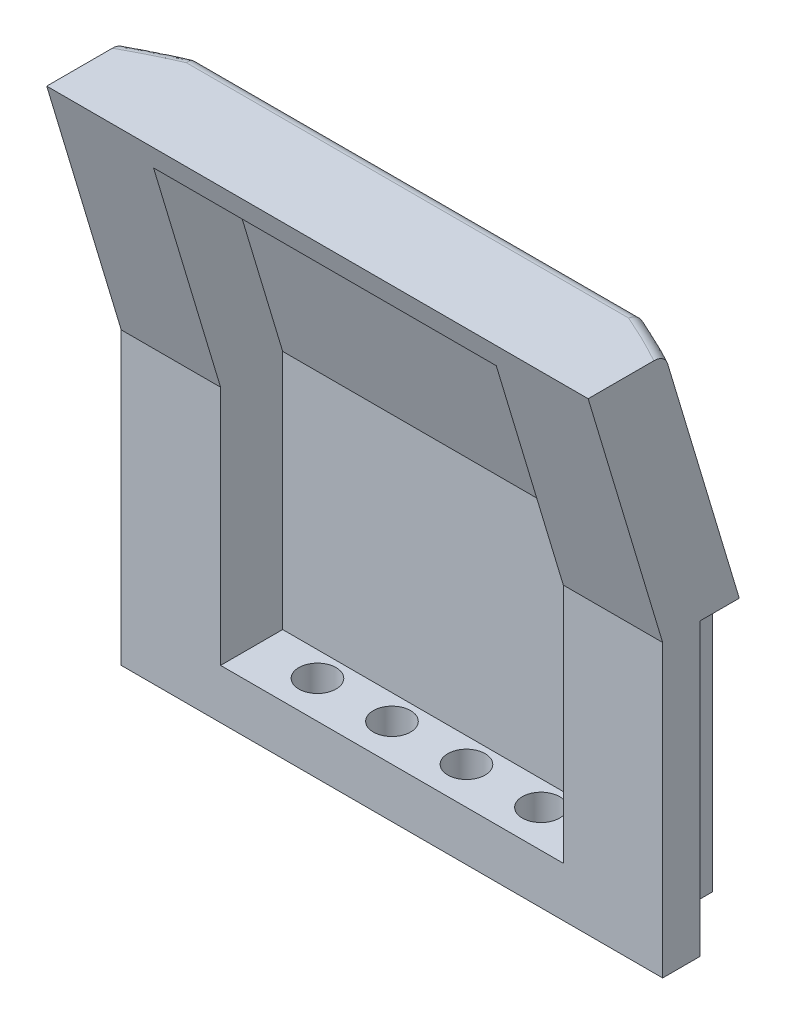
SolidWorks part; units mm, degrees
note: The reader was unsure of these and kept them because the rebuilt part matched: shared geometry of "Sketch1<4>", "Sketch1<7>", "Sketch2<5>", "Sketch2<6>", "Sketch2<7>", "Sketch2<8>".
ref_plane "Front Plane" through (0, 0, 0) normal (0, 0, 1) x (1, 0, 0)
ref_plane "Top Plane" through (0, 0, 0) normal (0, 1, 0) x (1, 0, 0)
ref_plane "Right Plane" through (0, 0, 0) normal (1, 0, 0) x (0, 0, -1)
sketch "Sketch1" plane through (0, 0, 0) normal (0, 1, 0) x (1, 0, 0)
  line L0 (0, 0) -> (3, 0) construction
  line L1 (3, 0) -> (6, 0) construction
  line L2 (6, 0) -> (9, 0) construction
  line L3 (13.4, 2.5) -> (-4.4, 2.5)
  line L4 (-6.4, -1.5) -> (15.4, -1.5)
  line L7 (-6.4, 0) -> (-6.4, -1.5)
  line L10 (13.4, 2.5) -> (13.4, 0)
  line L11 (13.4, 0) -> (15.4, 0)
  line L15 (-4.4, 1) -> (13.4, 1)
  line L16 (-2.4, -1.5) -> (-2.4, 1)
  line L17 (11.4, 1) -> (11.4, -1.5)
  line L18 (15.4, 0) -> (15.4, -1.5)
  line L19 (-4.4, 2.5) -> (-4.4, 0)
  line L20 (-4.4, 0) -> (-6.4, 0)
  circle A0 centre (3, 0) radius 0.75
  circle A1 centre (6, 0) radius 0.75
  circle A2 centre (9, 0) radius 0.75
  circle A3 centre (0, 0) radius 0.75
  circle A4 centre (0, 0) radius 1
  circle A5 centre (3, 0) radius 1
  circle A6 centre (6, 0) radius 1
  circle A7 centre (9, 0) radius 1
  point P29 (4.5, -1.5)
  point P30 (4.5, 0)
  dimension "D1" = 2
  dimension "D2" = 1.5
  dimension "D3" = 3
  dimension "D4" = 17.8
  dimension "D5" = 1.5
  dimension "D6" = 2
  dimension "D7" = 2
  dimension "D8" = 2
  dimension "D9" = 2.5
extrude "Boss-Extrude1" add sketch "Sketch1" along normal blind 1.7
extrude "Boss-Extrude2" add sketch "Sketch1<4>" against normal blind 0.3
sketch "Sketch1<4>" plane through (0, 0, 0) normal (0, 1, 0) x (1, 0, 0) same geometry as "Sketch1"
extrude "Boss-Extrude3" add sketch "Sketch1<7>" along normal blind 11.4
sketch "Sketch1<7>" plane through (0, 0, 0) normal (0, 1, 0) x (1, 0, 0) same geometry as "Sketch1"
sketch "Sketch2" plane through (-4.4, 0, 0) normal (-1, 0, 0) x (0, 0, 1)
  line L0 (-2.5, 11.4) -> (0.5, 21.4)
  line L1 (0.5, 21.4) -> (4.5, 21.4)
  line L2 (4.5, 21.4) -> (1.5, 11.4)
  line L3 (-2.5, 11.4) -> (1.5, 11.4)
  line L4 (-1, 11.4) -> (2, 21.4)
  line L5 (1.7, 20.4) -> (4.2, 20.4)
  line M6 (-2.5, 11.4) -> (-2.5, -0.3)
  line M7 (-2.5, -0.3) -> (0, -0.3)
  line M8 (0, -0.3) -> (0, 11.4)
  line M9 (0, 11.4) -> (-2.5, 11.4)
  dimension "D1" = 3
  dimension "D2" = 10
  dimension "D3" = 1.5
  dimension "D4" = 1
extrude "Boss-Extrude4" add sketch "Sketch2" against normal up to surface (19.8 mm away) contours L3 L4 L1 L0 | L4 L3 L2 L1 M9
extrude "Cut-Extrude1" cut sketch "Sketch2<5>" against normal up to surface (15.8 mm away) contours L4 L3 L2 L1 M9
sketch "Sketch2<5>" plane through (-4.4, 0, 0) normal (-1, 0, 0) x (0, 0, 1) same geometry as "Sketch2"
extrude "Boss-Extrude5" add sketch "Sketch2<6>" along direction (-1, 0, 0) on the side against the normal up to surface (2 mm away) contours L4 L3 L2 L1 M9 | L3 L4 L1 L0 | L3 M9 M6 M7 M8
sketch "Sketch2<6>" plane through (-4.4, 0, 0) normal (-1, 0, 0) x (0, 0, 1) same geometry as "Sketch2"
extrude "Boss-Extrude6" add sketch "Sketch2<7>" along normal up to surface (2 mm away) contours L4 L3 L2 L1 M9 | L3 L4 L1 L0
sketch "Sketch2<7>" plane through (-4.4, 0, 0) normal (-1, 0, 0) x (0, 0, 1) same geometry as "Sketch2"
ref_plane "Plane1" through (0, 19.7706, 5.9312) normal (0, 0.9578, 0.2873) x (1, 0, 0)
sketch "Sketch5" plane through (0, 19.7706, 5.9312) normal (0, 0.9578, 0.2873) x (1, 0, 0)
  line L0 (22.5, -25.3297) -> (26.5, -25.3297)
  line L1 (-17.5, -38.3297) -> (26.5, -38.3297)
  line L2 (-17.5, -38.3297) -> (-17.5, 5.6703)
  line L3 (-17.5, 5.6703) -> (26.5, 5.6703)
  line L4 (26.5, -38.3297) -> (26.5, 5.6703)
  line L5 (-17.5, -38.3297) -> (26.5, 5.6703) construction
  line L6 (-17.5, 5.6703) -> (26.5, -38.3297) construction
  line L7 (22.5, -7.3297) -> (26.5, -7.3297)
  line L8 (22.5, -25.3297) -> (22.5, -7.3297)
  line L9 (13.5, 5.6703) -> (13.5, 1.6703)
  line L10 (13.5, 1.6703) -> (-4.5, 1.6703)
  line L11 (-4.5, 1.6703) -> (-4.5, 5.6703)
  line L12 (-17.5, -7.3297) -> (-13.5, -7.3297)
  line L13 (-13.5, -7.3297) -> (-13.5, -25.3297)
  line L14 (-13.5, -25.3297) -> (-17.5, -25.3297)
  line L15 (-4.5, -38.3297) -> (-4.5, -34.3297)
  line L16 (-4.5, -34.3297) -> (13.5, -34.3297)
  line L17 (13.5, -34.3297) -> (13.5, -38.3297)
  line L18 (22.5, -7.3297) -> (22.5, -5.2297)
  line L19 (22.5, -5.2297) -> (24, -5.2297)
  line L20 (24, -5.2297) -> (24, -7.3297)
  line L21 (22.5, -25.3297) -> (22.5, -27.4297)
  line L22 (22.5, -27.4297) -> (24, -27.4297)
  line L23 (24, -27.4297) -> (24, -25.3297)
  line L24 (13.5, 1.6703) -> (15.6, 1.6703)
  line L25 (15.6, 1.6703) -> (15.6, 3.1703)
  line L26 (15.6, 3.1703) -> (13.5, 3.1703)
  line L27 (-4.5, 1.6703) -> (-6.6, 1.6703)
  line L28 (-6.6, 1.6703) -> (-6.6, 3.1703)
  line L29 (-6.6, 3.1703) -> (-4.5, 3.1703)
  line L30 (13.5, -34.3297) -> (15.6, -34.3297)
  line L31 (15.6, -34.3297) -> (15.6, -35.8297)
  line L32 (15.6, -35.8297) -> (13.5, -35.8297)
  line L33 (-4.5, -34.3297) -> (-6.6, -34.3297)
  line L34 (-6.6, -34.3297) -> (-6.6, -35.8297)
  line L35 (-6.6, -35.8297) -> (-4.5, -35.8297)
  line L36 (-13.5, -25.3297) -> (-13.5, -27.4297)
  line L37 (-13.5, -27.4297) -> (-15, -27.4297)
  line L38 (-15, -27.4297) -> (-15, -25.3297)
  line L39 (-13.5, -7.3297) -> (-13.5, -5.2297)
  line L40 (-13.5, -5.2297) -> (-15, -5.2297)
  line L41 (-15, -5.2297) -> (-15, -7.3297)
  line L42 (-15, -5.2297) -> (-16.5188, -5.2297)
  line L43 (-6.6, 3.1703) -> (-6.6, 4.6891)
  line L44 (15.6, 3.1703) -> (15.6, 4.6891)
  line L45 (24, -5.2297) -> (25.5188, -5.2297)
  line L46 (24, -27.4297) -> (25.5188, -27.4297)
  line L47 (15.6, -35.8297) -> (15.6, -37.3485)
  line L48 (-6.6, -35.8297) -> (-6.6, -37.3485)
  line L49 (-15, -27.4297) -> (-16.5188, -27.4297)
  line L51 (15.4, 5.6703) -> (-6.4, 5.6703) construction
  arc A0 (13.5, 5.6703) -> (26.5, -7.3297) centre (4.5, -16.3297) cw
  arc A1 (26.5, -25.3297) -> (13.5, -38.3297) centre (4.5, -16.3297) cw
  arc A2 (-4.5, -38.3297) -> (-17.5, -25.3297) centre (4.5, -16.3297) cw
  arc A3 (-17.5, -7.3297) -> (-4.5, 5.6703) centre (4.5, -16.3297) cw
  point P0 (4.5, -16.3297)
  point P54 (4.5, 5.6703)
  point P57 (4.5, 5.6703)
  dimension "D1" = 44
  dimension "D2" = 18
  dimension "D3" = 4
  dimension "D4" = 2.1
  dimension "D5" = 1.5
extrude "Cut-Extrude4" cut sketch "Sketch5" against normal blind 12 and the other way blind 10 contours L2 A3 L3 | L3 A0 L4
extrude "Boss-Extrude7" add sketch "Sketch2<8>" along normal up to surface and the other way up to surface contours L4 L5 L2 L1 up to face at (-6.4, 13.0222, 1.1923) other way up to face at (15.4, 13.0222, 1.1923)
sketch "Sketch2<8>" plane through (-4.4, 0, 0) normal (-1, 0, 0) x (0, 0, 1) same geometry as "Sketch2"
fillet "Fillet1" radius 0.5 3 edges at (4.5, 21.4, 0.5) (-5.4597, 21.4, 0.9359) (14.4597, 21.4, 0.9359)
